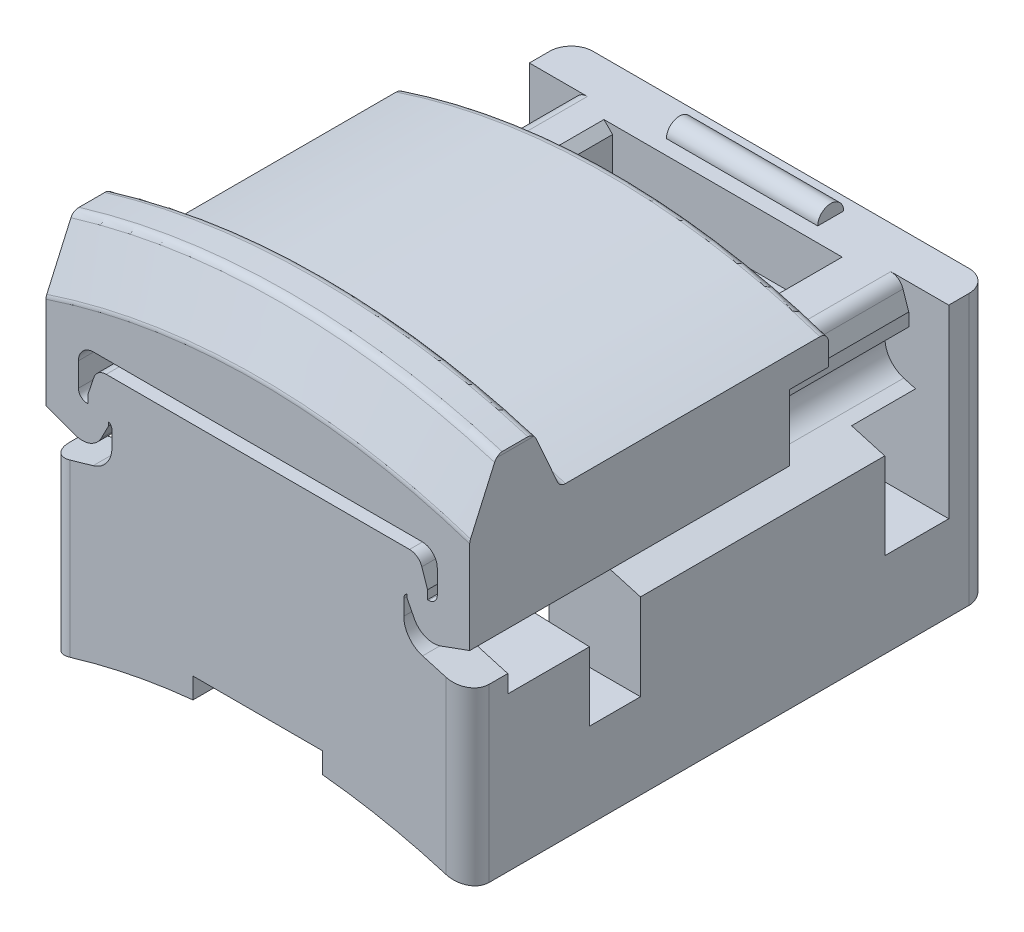
SolidWorks part; units mm, degrees
ref_plane "Ebene vorne" through (0, 0, 0) normal (0, 0, 1) x (1, 0, 0)
ref_plane "Ebene oben" through (0, 0, 0) normal (0, 1, 0) x (1, 0, 0)
ref_plane "Ebene rechts" through (0, 0, 0) normal (1, 0, 0) x (0, 0, -1)
ref_plane "Ebene1" through (0, 0, 7.1) normal (0, 0, 1) x (1, 0, 0)
sketch "Skizze1" plane through (0, 0, 7.1) normal (0, 0, 1) x (1, 0, 0)
  line L0 (-4.9, 8.4707) -> (-4.9, 4.92)
  line L1 (-4.9, 4.92) -> (-4.2344, 4.6777)
  line L2 (-3.6178, 4.9206) -> (-3.45, 5.25)
  line L3 (-3.45, 5.25) -> (-3.45, 5.45)
  line L4 (-3.45, 5.45) -> (-3.95, 5.45)
  line L5 (-4.15, 5.65) -> (-4.15, 6.2)
  line L6 (-3.8, 6.55) -> (3.8, 6.55)
  line L7 (4.15, 6.2) -> (4.15, 5.65)
  line L8 (3.95, 5.45) -> (3.45, 5.45)
  line L9 (3.45, 5.45) -> (3.45, 5.25)
  line L10 (3.45, 5.25) -> (3.6178, 4.9206)
  line L11 (4.2344, 4.6777) -> (4.9, 4.92)
  line L12 (4.9, 4.92) -> (4.9, 8.4707)
  arc A0 (-4.2344, 4.6777) -> (-3.6178, 4.9206) centre (-4.0634, 5.1476) ccw
  arc A1 (-3.95, 5.45) -> (-4.15, 5.65) centre (-3.95, 5.65) cw
  arc A2 (-4.15, 6.2) -> (-3.8, 6.55) centre (-3.8, 6.2) cw
  arc A3 (3.8, 6.55) -> (4.15, 6.2) centre (3.8, 6.2) cw
  arc A4 (4.15, 5.65) -> (3.95, 5.45) centre (3.95, 5.65) cw
  arc A5 (3.6178, 4.9206) -> (4.2344, 4.6777) centre (4.0634, 5.1476) ccw
  arc A6 (4.9, 8.4707) -> (4.7566, 8.6626) centre (4.7, 8.4707) ccw
  arc A7 (4.7566, 8.6626) -> (-4.7566, 8.6626) centre (0, -7.45) ccw
  arc A8 (-4.7566, 8.6626) -> (-4.9, 8.4707) centre (-4.7, 8.4707) ccw
extrude "Aufsatz-Linear austragen1" add sketch "Skizze1" against normal blind 8.3
sketch "Skizze2" plane through (0, 0, 0) normal (1, 0, 0) x (0, 0, -1)
  line L0 (-7.1, 12) -> (-7.1, 7.8546)
  line L1 (-7.0813, 7.9391) -> (-6.5238, 9.1345)
  line L2 (-6.3426, 9.25) -> (-5.7474, 9.25)
  line L3 (-5.5662, 9.1345) -> (-5.0676, 8.0655)
  line L4 (-4.8864, 7.95) -> (1, 7.95)
  line L5 (1.2, 7.75) -> (1.2, 12)
  line L6 (1.2, 12) -> (-7.1, 12)
  line L7 (1.2, -7.6) -> (-7.1, -7.6) construction
  arc A0 (-7.1, 7.8546) -> (-7.0813, 7.9391) centre (-6.9, 7.8546) cw
  arc A1 (-6.5238, 9.1345) -> (-6.3426, 9.25) centre (-6.3426, 9.05) cw
  arc A2 (-5.7474, 9.25) -> (-5.5662, 9.1345) centre (-5.7474, 9.05) cw
  arc A3 (-5.0676, 8.0655) -> (-4.8864, 7.95) centre (-4.8864, 8.15) ccw
  arc A4 (1, 7.95) -> (1.2, 7.75) centre (1, 7.75) cw
revolve "Schnitt-Rotation1" cut sketch "Skizze2" angle 30 about L7 other way angle 30 reverse direction yes
sketch "Skizze3" plane through (0, 0, 0) normal (1, 0, 0) x (0, 0, -1)
  line L0 (0.3, 6.45) -> (0.3, 3.55)
  line L1 (0.3, 3.55) -> (1.2, 3.55)
  line L2 (1.2, 3.55) -> (1.2, 6.45)
  line L3 (1.2, 6.45) -> (0.3, 6.45)
extrude "Schnitt-Linear austragen1" cut sketch "Skizze3" along normal blind 5 and the other way blind 5
ref_plane "Ebene2" through (0, 0, 7.1) normal (0, 0, 1) x (1, 0, 0)
sketch "Skizze4" plane through (0, 0, 7.1) normal (0, 0, 1) x (1, 0, 0)
  line L0 (-4.85, 3.97) -> (-4.85, 0)
  line L1 (4.85, 0) -> (4.85, 3.97)
  line L2 (4.85, 3.97) -> (3.8096, 4.2683)
  line L3 (3.375, 4.8451) -> (3.375, 5.2)
  line L4 (3.525, 5.35) -> (3.925, 5.35)
  line L5 (3.925, 5.35) -> (3.925, 5.65)
  line L6 (3.925, 5.65) -> (3.7928, 6.0452)
  line L7 (3.5083, 6.25) -> (-3.5083, 6.25)
  line L8 (-3.7928, 6.0452) -> (-3.925, 5.65)
  line L9 (-3.925, 5.65) -> (-3.925, 5.35)
  line L10 (-3.925, 5.35) -> (-3.525, 5.35)
  line L11 (-3.375, 5.2) -> (-3.375, 4.8451)
  line L12 (-3.8096, 4.2683) -> (-4.85, 3.97)
  arc A0 (-4.85, 0) -> (4.85, 0) centre (0, -14.1943) cw
  arc A1 (3.8096, 4.2683) -> (3.375, 4.8451) centre (3.975, 4.8451) cw
  arc A2 (3.375, 5.2) -> (3.525, 5.35) centre (3.525, 5.2) cw
  arc A3 (3.7928, 6.0452) -> (3.5083, 6.25) centre (3.5083, 5.95) ccw
  arc A4 (-3.5083, 6.25) -> (-3.7928, 6.0452) centre (-3.5083, 5.95) ccw
  arc A5 (-3.525, 5.35) -> (-3.375, 5.2) centre (-3.525, 5.2) cw
  arc A6 (-3.375, 4.8451) -> (-3.8096, 4.2683) centre (-3.975, 4.8451) cw
extrude "Aufsatz-Linear austragen2" add sketch "Skizze4" against normal blind 12.1
ref_plane "Ebene3" through (0, 0, -5) normal (0, 0, 1) x (1, 0, 0)
sketch "Skizze5" plane through (0, 0, -5) normal (0, 0, 1) x (1, 0, 0)
  line L0 (4.85, 0) -> (4.85, 6.25)
  line L1 (4.85, 6.25) -> (-4.85, 6.25)
  line L2 (-4.85, 6.25) -> (-4.85, 0)
  arc A0 (-4.85, 0) -> (4.85, 0) centre (0, -14.1943) cw
extrude "Aufsatz-Linear austragen3" add sketch "Skizze5" along normal blind 0.97
sketch "Skizze6" plane through (0, 0, 0) normal (0, 0, 1) x (1, 0, 0)
  line L0 (0, 3.96) -> (3.1, 3.96)
  line L1 (3.25, 3.81) -> (3.25, 3.68)
  line L2 (3.25, 3.68) -> (3.83, 3.68)
  line L3 (4.13, 3.38) -> (4.13, 0)
  line L4 (4.13, 0) -> (0, 0)
  line L5 (0, 0) -> (0, 3.96)
  line L6 (0, 0) -> (0, 3.96) construction
  arc A0 (3.1, 3.96) -> (3.25, 3.81) centre (3.1, 3.81) cw
  arc A1 (3.83, 3.68) -> (4.13, 3.38) centre (3.83, 3.38) cw
revolve "Schnitt-Rotation2" cut sketch "Skizze6" angle 360 about L6 reverse direction yes
sketch "Skizze7" plane through (0, 0, 7.1) normal (0, 0, 1) x (1, 0, 0)
  line L0 (-1.5, 0.21) -> (1.5, 0.21)
  line L1 (1.5, 0.21) -> (1.5, 1.21)
  line L2 (1.5, 1.21) -> (-1.5, 1.21)
  line L3 (-1.5, 1.21) -> (-1.5, 0.21)
extrude "Schnitt-Linear austragen2" cut sketch "Skizze7" against normal blind 2.38
sketch "Skizze8" plane through (0, 0, 0) normal (0, 1, 0) x (1, 0, 0)
  line L0 (-7, 4.5) -> (-4.85, 4.5)
  line L1 (-4.35, 5) -> (4.35, 5)
  line L2 (4.85, 4.5) -> (7, 4.5)
  line L3 (7, 4.5) -> (7, 7)
  line L4 (7, 7) -> (-7, 7)
  line L5 (-7, 7) -> (-7, 4.5)
  arc A0 (-4.85, 4.5) -> (-4.35, 5) centre (-4.35, 4.5) cw
  arc A1 (4.35, 5) -> (4.85, 4.5) centre (4.35, 4.5) cw
extrude "Schnitt-Linear austragen3" cut sketch "Skizze8" along normal blind 6.25
sketch "Skizze9" plane through (0, 0, 0) normal (0, 1, 0) x (1, 0, 0)
  line L0 (-7, -6.6) -> (-7, -9)
  line L1 (-7, -9) -> (7, -9)
  line L2 (7, -9) -> (7, -6.6)
  line L3 (7, -6.6) -> (4.85, -6.6)
  line L4 (4.35, -7.1) -> (-4.35, -7.1)
  line L5 (-4.85, -6.6) -> (-7, -6.6)
  arc A0 (4.85, -6.6) -> (4.35, -7.1) centre (4.35, -6.6) cw
  arc A1 (-4.35, -7.1) -> (-4.85, -6.6) centre (-4.35, -6.6) cw
extrude "Schnitt-Linear austragen4" cut sketch "Skizze9" along normal blind 4.2
sketch "Skizze10" plane through (0, 0, 0) normal (1, 0, 0) x (0, 0, -1)
  circle A0 centre (4.4, 6.25) radius 0.3
extrude "Aufsatz-Linear austragen4" add sketch "Skizze10" against normal blind 1.75 and the other way blind 1.75
ref_plane "Ebene4" through (0, 0, 6.17) normal (0, 0, 1) x (1, 0, 0)
sketch "Skizze11" plane through (0, 0, 6.17) normal (0, 0, 1) x (1, 0, 0)
  line L0 (-2.855, 6.25) -> (-2.655, 6.05)
  line L1 (-2.655, 6.05) -> (-2.655, 4.95)
  line L2 (-2.655, 4.95) -> (2.655, 4.95)
  line L3 (2.655, 4.95) -> (2.655, 6.25)
  line L4 (2.655, 6.25) -> (-2.855, 6.25)
extrude "Schnitt-Linear austragen5" cut sketch "Skizze11" against normal blind 9.93
ref_plane "Ebene5" through (0, 4.95, 0) normal (0, 1, 0) x (1, 0, 0)
sketch "Skizze12" plane through (0, 4.95, 0) normal (0, 1, 0) x (1, 0, 0)
  line L0 (-2.655, -6.17) -> (2.655, -6.17)
  line L1 (2.655, -6.17) -> (2.655, 0.03)
  line L2 (0.655, 2.03) -> (-0.655, 2.03)
  line L3 (-2.655, 0.03) -> (-2.655, -6.17)
  arc A0 (2.655, 0.03) -> (0.655, 2.03) centre (0.655, 0.03) ccw
  arc A1 (-0.655, 2.03) -> (-2.655, 0.03) centre (-0.655, 0.03) ccw
extrude "Schnitt-Linear austragen6" cut sketch "Skizze12" against normal blind 1.5
sketch "Skizze13" plane through (0, 0, 0) normal (1, 0, 0) x (0, 0, -1)
  line L0 (2.55, 4.19) -> (2.55, 1.97)
  line L1 (2.55, 1.97) -> (4.03, 1.97)
  line L2 (4.03, 1.97) -> (4.03, 4.19)
  line L3 (4.03, 4.19) -> (2.55, 4.19)
extrude "Schnitt-Linear austragen7" cut sketch "Skizze13" along normal blind 5 and the other way blind 5
sketch "Skizze14" plane through (0, 0, 0) normal (1, 0, 0) x (0, 0, -1)
  line L0 (-6.17, 3.48) -> (-4.28, 3.48)
  line L1 (-4.28, 3.48) -> (-4.28, 1.97)
  line L2 (-4.28, 1.97) -> (-3.1, 1.97)
  line L3 (-3.1, 1.97) -> (-3.1, 4.45)
  line L4 (-3.1, 4.45) -> (-6.17, 4.45)
  line L5 (-6.17, 4.45) -> (-6.17, 3.48)
extrude "Schnitt-Linear austragen8" cut sketch "Skizze14" along normal blind 5 and the other way blind 5
sketch "Skizze15" plane through (0, 0, 0) normal (1, 0, 0) x (0, 0, -1)
  line L0 (-6.17, 4.75) -> (-6.17, 4.35)
  line L1 (-6.17, 4.35) -> (-3.1, 4.35)
  line L2 (-3.1, 4.35) -> (-3.1, 4.75)
  line L3 (-3.1, 4.75) -> (-6.17, 4.75)
extrude "Schnitt-Linear austragen9" cut sketch "Skizze15" along normal blind 3.6 and the other way blind 3.6
ref_plane "Ebene6" through (0, 0, 6.4) normal (0, 0, 1) x (1, 0, 0)
sketch "Skizze16" plane through (0, 0, 6.4) normal (0, 0, 1) x (1, 0, 0)
  line L0 (-4.85, 1.74) -> (4.85, 1.74)
  line L1 (4.85, 1.74) -> (4.85, 3.5614)
  line L2 (4.85, 3.5614) -> (2.6, 3.64)
  line L3 (2.6, 3.64) -> (-2.6, 3.64)
  line L4 (-2.6, 3.64) -> (-4.85, 3.5614)
  line L5 (-4.85, 3.5614) -> (-4.85, 1.74)
extrude "Aufsatz-Linear austragen5" add sketch "Skizze16" against normal blind 2.12
sketch "Skizze17" plane through (0, 0, 0) normal (1, 0, 0) x (0, 0, -1)
  line L0 (-6.5, 5.17) -> (-6.5, 3.8)
  line L1 (-6.5, 3.8) -> (-6.17, 3.8)
  line L2 (-5.67, 4.3) -> (-2.3076, 4.3)
  line L3 (-1.9002, 4.3868) -> (0.19, 5.3193)
  line L4 (0.19, 5.3193) -> (0.19, 6.22)
  line L5 (0.19, 6.22) -> (0, 6.22)
  line L6 (0, 6.22) -> (-2.9786, 4.8938)
  line L7 (-2.9786, 4.8938) -> (-4.62, 4.67)
  line L8 (-4.62, 4.67) -> (-5.67, 4.67)
  line L9 (-6.17, 5.17) -> (-6.5, 5.17)
  arc A0 (-6.17, 3.8) -> (-5.67, 4.3) centre (-5.67, 3.8) cw
  arc A1 (-2.3076, 4.3) -> (-1.9002, 4.3868) centre (-2.3076, 5.3) ccw
  arc A2 (-5.67, 4.67) -> (-6.17, 5.17) centre (-5.67, 5.17) cw
extrude "Aufsatz-Linear austragen6" add sketch "Skizze17" against normal blind 1.965 and the other way blind 1.965
sketch "Skizze18" plane through (0, 0, 0) normal (1, 0, 0) x (0, 0, -1)
  line L0 (0.19, 3.42) -> (-1.31, 3.42)
  line L1 (-1.31, 3.42) -> (-1.31, 6.22)
  line L2 (-1.31, 6.22) -> (0.19, 6.22)
  line L3 (0.19, 6.22) -> (0.19, 3.42)
  line L4 (0.19, 6.22) -> (0.19, 3.42) construction
revolve "Rotation1" add sketch "Skizze18" angle 360 about L4 reverse direction yes
sketch "Skizze19" plane through (0, 0, 0) normal (1, 0, 0) x (0, 0, -1)
  line L0 (-1.5, 5.5522) -> (0, 6.22)
  line L1 (0, 6.22) -> (0, 7.22)
  line L2 (0, 7.22) -> (-1.5, 7.22)
  line L3 (-1.5, 7.22) -> (-1.5, 5.5522)
extrude "Schnitt-Linear austragen10" cut sketch "Skizze19" along normal blind 1.5 and the other way blind 1.5
sketch "Skizze20" plane through (0, 0, 0) normal (1, 0, 0) x (0, 0, -1)
  line L0 (0.19, 6.22) -> (1.5558, 3.92)
  line L1 (1.5558, 3.92) -> (1.69, 3.92)
  line L2 (1.69, 3.92) -> (1.69, 6.22)
  line L3 (1.69, 6.22) -> (0.19, 6.22)
extrude "Schnitt-Linear austragen11" cut sketch "Skizze20" along normal blind 1.5 and the other way blind 1.5
sketch "Skizze21" plane through (0, 0, 0) normal (1, 0, 0) x (0, 0, -1)
  line L0 (0.19, 3.92) -> (1.69, 3.92)
  line L1 (1.69, 3.92) -> (1.69, 6.22)
  line L2 (1.69, 6.22) -> (0.19, 6.22)
  line L3 (0.19, 6.22) -> (0.19, 3.92)
extrude "Schnitt-Linear austragen12" cut sketch "Skizze21" along normal blind 0.65 and the other way blind 0.65
sketch "Skizze22" plane through (0, 0, 0) normal (1, 0, 0) x (0, 0, -1)
  line L0 (-0.6129, 3.61) -> (-0.55, 1.81)
  line L1 (-0.55, 1.81) -> (0.95, 1.81)
  line L2 (0.95, 1.81) -> (1.0129, 3.61)
  line L3 (1.0129, 3.61) -> (-0.6129, 3.61)
extrude "Aufsatz-Linear austragen7" add sketch "Skizze22" against normal blind 0.4 and the other way blind 0.4
ref_plane "Ebene7" through (0, 3.62, 0) normal (0, 1, 0) x (1, 0, 0)
ref_plane "ANBAU XY" through (0, 3.62, 0) normal (0, -1, 0) x (-1, 0, 0)
ref_plane "ANBAU XZ" through (0, 0, 0) normal (0, 0, -1) x (-1, 0, 0)
ref_plane "ANBAU YZ" through (0, 0, 0) normal (1, 0, 0) x (0, 0, -1)
ref_axis "ANBAU X" through (-80.9, 3.62, 0) along (1, 0, 0)
ref_axis "ANBAU Y" through (0, 3.62, -50) along (0, 0, 1)
ref_axis "ANBAU Z" through (0, -50, 0) along (0, 1, 0)
sketch3d "ANBAU"
  point P0 (0, 3.62, 0)
